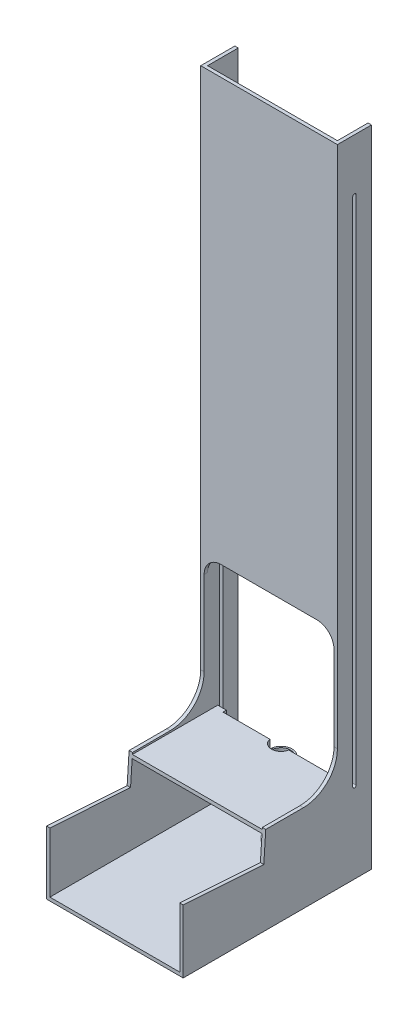
SolidWorks part; units mm, degrees
material "AISI 4340 Steel, annealed"
ref_plane "Front Plane" through (0, 0, 0) normal (0, 0, 1) x (1, 0, 0)
ref_plane "Top Plane" through (0, 0, 0) normal (0, 1, 0) x (1, 0, 0)
ref_plane "Right Plane" through (0, 0, 0) normal (1, 0, 0) x (0, 0, -1)
ref_plane "Right side of elevator platform" through (190.5, 0, 0) normal (1, 0, 0) x (0, 0, -1)
sketch "Sketch2" plane through (190.5, 0, 0) normal (1, 0, 0) x (0, 0, -1)
  line L0 (50, 236.5) -> (50, 1736.5) construction
  line L1 (45, 236.5) -> (45, 1736.5)
  line L2 (55, 236.5) -> (55, 1736.5)
  line L4 (0, 0) -> (100, 0)
  line L5 (0, 0) -> (0, 1800)
  line L6 (0, 1800) -> (100, 1800)
  line L7 (100, 0) -> (100, 1800)
  arc A0 (45, 236.5) -> (55, 236.5) centre (50, 236.5) ccw
  arc A1 (55, 1736.5) -> (45, 1736.5) centre (50, 1736.5) ccw
  point P2 (50, 986.5)
  dimension "D6" = 5
  dimension "D1" = 1800
  dimension "D2" = 100
  dimension "D3" = 50
  dimension "D4" = 236.5
  dimension "D5" = 63.5
extrude "Right side guide" add sketch "Sketch2" along normal blind 10
sketch "Sketch3" plane through (190.5, 0, 0) normal (-1, 0, 0) x (0, 0, 1)
  line L0 (0, 1800) -> (0, 0) construction
  line L1 (-100, 0) -> (0, 0)
  line L2 (-100, 0) -> (-100, 10)
  line L3 (-100, 10) -> (0, 10)
  line L4 (0, 0) -> (0, 10)
  dimension "D1" = 10
extrude "Bottom connection" add sketch "Sketch3" along normal blind 381
sketch "Sketch4" plane through (-190.5, 0, 0) normal (-1, 0, 0) x (0, 0, 1)
  line L0 (-55, 236.5) -> (-55, 1736.5) construction
  line L1 (-45, 1736.5) -> (-45, 236.5) construction
  line L2 (-55, 236.5) -> (-55, 1736.5)
  line L3 (-45, 1736.5) -> (-45, 236.5)
  line L4 (-100, 10) -> (0, 10)
  line L5 (0, 10) -> (0, 1800)
  line L6 (0, 1800) -> (-100, 1800)
  line L7 (-100, 1800) -> (-100, 10)
  line L9 (0, 10) -> (0, 1800)
  line L10 (0, 1800) -> (-100, 1800)
  line L11 (-100, 1800) -> (-100, 10)
  line L16 (-100, 10) -> (-100, 0)
  line L17 (-100, 0) -> (0, 0)
  line L18 (0, 0) -> (0, 10)
  line L19 (0, 10) -> (-100, 10)
  line L20 (-100, 10) -> (-100, 0)
  line L21 (-100, 0) -> (0, 0)
  line L22 (0, 0) -> (0, 10)
  arc A0 (-45, 1736.5) -> (-55, 1736.5) centre (-50, 1736.5) ccw construction
  arc A1 (-55, 236.5) -> (-45, 236.5) centre (-50, 236.5) ccw construction
  arc A2 (-45, 1736.5) -> (-55, 1736.5) centre (-50, 1736.5) ccw
  arc A3 (-55, 236.5) -> (-45, 236.5) centre (-50, 236.5) ccw
  dimension "D1" = 0
  dimension "D2" = 0
extrude "Left side guide" add sketch "Sketch4" along normal blind 10
sketch "Sketch5" plane through (0, 0, 0) normal (0, 0, 1) x (1, 0, 0)
  line L0 (-190.5, 10) -> (-190.5, 1800) construction
  line L1 (-190.5, 1800) -> (190.5, 1800)
  line L2 (-190.5, 1800) -> (-190.5, 653.8)
  line L3 (-190.5, 653.8) -> (190.5, 653.8)
  line L4 (190.5, 1800) -> (190.5, 653.8)
  line L5 (190.5, 1800) -> (190.5, 10) construction
  line L6 (200.5, 1800) -> (190.5, 1800) construction
  line L7 (-190.5, 10) -> (190.5, 10) construction
  dimension "D1" = 643.8
extrude "Structural webbing extrude" add sketch "Sketch5" against normal blind 10
sketch "Sketch6" plane through (0, 0, 0) normal (0, 0, 1) x (1, 0, 0)
  line L0 (-200.5, 251.5) -> (-200.5, 0)
  line L1 (-200.5, 0) -> (-200.5, 1800) construction
  line L2 (-200.5, 0) -> (200.5, 0)
  line L3 (200.5, 0) -> (200.5, 251.5)
  line L4 (200.5, 1800) -> (200.5, 0) construction
  line L5 (200.5, 251.5) -> (190.5, 251.5)
  line L6 (190.5, 653.8) -> (190.5, 10) construction
  line L7 (190.5, 251.5) -> (190.5, 10)
  line L8 (190.5, 10) -> (-190.5, 10)
  line L9 (-190.5, 10) -> (-190.5, 251.5)
  line L10 (-190.5, 10) -> (-190.5, 653.8) construction
  line L11 (-190.5, 251.5) -> (-200.5, 251.5)
  dimension "D1" = 241.5
extrude "Input roller holder extrude" add sketch "Sketch6" along normal blind 452.52
sketch "Sketch7" plane through (190.5, 0, 0) normal (-1, 0, 0) x (0, 0, 1)
  line L0 (0, 653.8) -> (0, 251.5) construction
  line L1 (452.52, 251.5) -> (-40, 251.5)
  line L2 (452.52, 251.5) -> (452.52, 241.5)
  line L3 (452.52, 241.5) -> (-40, 241.5)
  line L4 (-40, 251.5) -> (-40, 241.5)
  dimension "D1" = 40
  dimension "D2" = 10
extrude "Input roller platform" add sketch "Sketch7" along normal up to next
sketch "Sketch8" plane through (0, 251.5, 0) normal (0, 1, 0) x (1, 0, 0)
  line L1 (-200.5, -452.52) -> (-190.5, -452.52)
  line L2 (-200.5, -452.52) -> (-200.5, 0)
  line L3 (-200.5, 0) -> (-190.5, 0)
  line L4 (-190.5, -452.52) -> (-190.5, 0)
  line L5 (190.5, 0) -> (200.5, 0)
  line L6 (190.5, 0) -> (190.5, -452.52)
  line L7 (190.5, -452.52) -> (200.5, -452.52)
  line L8 (200.5, 0) -> (200.5, -452.52)
extrude "Siding outline" add sketch "Sketch8" along normal blind 5
sketch "Sketch9" plane through (0, 1800, 0) normal (0, 1, 0) x (1, 0, 0)
  line L8 (190.5, 100) -> (190.5, 10)
  line L9 (190.5, 10) -> (-190.5, 10)
  line L10 (-190.5, 10) -> (-190.5, 100)
  line L11 (-190.5, 100) -> (-200.5, 100)
  line L12 (-200.5, 100) -> (-200.5, 0)
  line L13 (-200.5, 0) -> (200.5, 0)
  line L14 (200.5, 0) -> (200.5, 100)
  line L15 (200.5, 100) -> (190.5, 100)
  line L16 (190.5, 100) -> (190.5, 10)
  line L17 (190.5, 10) -> (-190.5, 10)
  line L18 (-190.5, 10) -> (-190.5, 100)
  line L19 (-190.5, 100) -> (-200.5, 100)
  line L20 (-200.5, 100) -> (-200.5, 0)
  line L21 (-200.5, 0) -> (200.5, 0)
  line L22 (200.5, 0) -> (200.5, 100)
  line L23 (200.5, 100) -> (190.5, 100)
  dimension "D1" = 0
extrude "Lip to prevent box from falling out" add sketch "Sketch9" along normal blind 91.5
fillet "Vertical section fillets" radius 100 2 edges at (195.5, 256.5, 0) (-195.5, 256.5, 0)
fillet "Smaller fillets" radius 50 2 edges at (190.5, 653.8, -5) (-190.5, 653.8, -5)
sketch "Sketch11" plane through (0, 0, -40) normal (0, 0, -1) x (-1, 0, 0)
  line L0 (190.5, 251.5) -> (-190.5, 251.5) construction
  line L1 (-165.5, 251.5) -> (165.5, 251.5)
  line L2 (-165.5, 251.5) -> (-165.5, 241.5)
  line L3 (-165.5, 241.5) -> (165.5, 241.5)
  line L4 (165.5, 251.5) -> (165.5, 241.5)
  line L5 (190.5, 241.5) -> (-190.5, 241.5) construction
  line L6 (-190.5, 251.5) -> (-190.5, 241.5) construction
  line L7 (190.5, 251.5) -> (190.5, 241.5) construction
  dimension "D1" = 25
  dimension "D2" = 25
extrude "Gate spacing cut" cut sketch "Sketch11" against normal blind 10
sketch "Sketch12" plane through (-190.5, 0, 0) normal (1, 0, 0) x (0, 0, -1)
  line L1 (45, 221.5) -> (40, 221.5)
  line L2 (45, 221.5) -> (45, 10)
  line L3 (45, 10) -> (40, 10)
  line L4 (40, 221.5) -> (40, 10)
  line L5 (100, 1891.5) -> (100, 10) construction
  line L6 (45, 236.5) -> (45, 1736.5) construction
  line L7 (-452.52, 10) -> (100, 10) construction
  line L8 (40, 241.5) -> (-452.52, 241.5) construction
  line L9 (30, 241.5) -> (25, 241.5)
  line L10 (30, 241.5) -> (30, 10)
  line L11 (30, 10) -> (25, 10)
  line L12 (25, 241.5) -> (25, 10)
  dimension "D1" = 60
  dimension "D2" = 20
  dimension "D3" = 5
extrude "Gate guide rails" add sketch "Sketch12" along normal up to next
sketch "Sketch13" plane through (0, 0, -45) normal (0, 0, -1) x (-1, 0, 0)
  line L0 (-190.5, 221.5) -> (190.5, 221.5) construction
  line L1 (-150.5, 221.5) -> (150.5, 221.5)
  line L2 (-150.5, 221.5) -> (-150.5, 10)
  line L3 (-150.5, 10) -> (150.5, 10)
  line L4 (150.5, 221.5) -> (150.5, 10)
  line L5 (190.5, 10) -> (-190.5, 10) construction
  line L6 (-190.5, 10) -> (-190.5, 1891.5) construction
  point P8 (0, 221.5)
  dimension "D1" = 40
extrude "Gate rod connection cutout" cut sketch "Sketch13" against normal through all
sketch "Sketch14" plane through (0, 10, 0) normal (0, 1, 0) x (1, 0, 0)
  line L0 (150.5, 45) -> (-150.5, 25) construction
  circle A0 centre (0, 35) radius 28
  circle A1 centre (0, 35) radius 33
  point P7 (0, 35)
  dimension "D1" = 56
  dimension "D2" = 5
extrude "Spring cup" add sketch "Sketch14" along normal blind 75
sketch "Sketch15" plane through (0, 85, 0) normal (0, 1, 0) x (1, 0, 0)
  line L0 (190.5, 30) -> (150.5, 30) construction
  line L1 (32.619, 30) -> (27.55, 30)
  line L3 (32.619, 40) -> (27.55, 40)
  line L5 (-27.55, 40) -> (-32.619, 40)
  line L6 (-27.55, 30) -> (-32.619, 30)
  circle A0 centre (0, 35) radius 28 construction
  arc A1 (27.55, 40) -> (-27.55, 40) centre (0, 35) ccw
  circle A2 centre (0, 35) radius 33 construction
  arc A3 (32.619, 40) -> (-32.619, 40) centre (0, 35) ccw
  arc A4 (-27.55, 30) -> (27.55, 30) centre (0, 35) ccw
  arc A5 (-32.619, 30) -> (32.619, 30) centre (0, 35) ccw
extrude "Spring container extension" add sketch "Sketch15" along normal up to surface (136.5 mm away) up to face at (0, 221.5, -27.5)
sketch "Sketch16" plane through (0, 221.5, 0) normal (0, 1, 0) x (1, 0, 0)
  circle A0 centre (0, 35) radius 28
  arc A1 (27.55, 40) -> (-27.55, 40) centre (0, 35) ccw construction
extrude "Spring hole (can't insert spring without this)" cut sketch "Sketch16" along normal up to surface (30 mm away) up to face at (0, 251.5, 85.63)
sketch "Sketch17" plane through (0, 221.5, 0) normal (0, 1, 0) x (1, 0, 0)
  line L2 (-26.1534, 25) -> (-31.4484, 25)
  line L3 (31.4484, 25) -> (26.1534, 25)
  line L4 (-26.1534, 25) -> (-31.4484, 25)
  line L5 (31.4484, 25) -> (26.1534, 25)
  arc A2 (-31.4484, 25) -> (31.4484, 25) centre (0, 35) ccw
  arc A3 (-26.1534, 25) -> (26.1534, 25) centre (0, 35) ccw
  arc A4 (-31.4484, 25) -> (31.4484, 25) centre (0, 35) ccw
  arc A5 (-26.1534, 25) -> (26.1534, 25) centre (0, 35) ccw
  dimension "D1" = 0
extrude "Container extension to meet with conveyor plate" add sketch "Sketch17" along normal up to next
fillet "Spring holder fillets" radius 10 4 edges at (0, 10, -68) (-31.4484, 231.5, -25) (31.4484, 231.5, -25) (0, 241.5, -2)
sketch "Sketch18" plane through (200.5, 0, 0) normal (1, 0, 0) x (0, 0, -1)
  line L0 (-452.52, 256.5) -> (-210.2672, 256.5)
  line L1 (-452.52, 256.5) -> (-100, 256.5) construction
  line L2 (-207.0894, 304.825) -> (-215.631, 174.9305) construction
  line L3 (-210.2672, 256.5) -> (-215.9435, 170.1783)
  line L4 (-215.9435, 170.1783) -> (-452.52, 185.7352)
  line L5 (-452.52, 0) -> (-452.52, 256.5) construction
  line L6 (-452.52, 185.7352) -> (-452.52, 256.5)
  line L7 (-228.6162, 171.0116) -> (-1641.6144, 263.9283) construction
  point P13 (-168.9443, 167.0877)
extrude "Cut-Extrude1" cut sketch "Sketch18" against normal through all both and the other way through all
